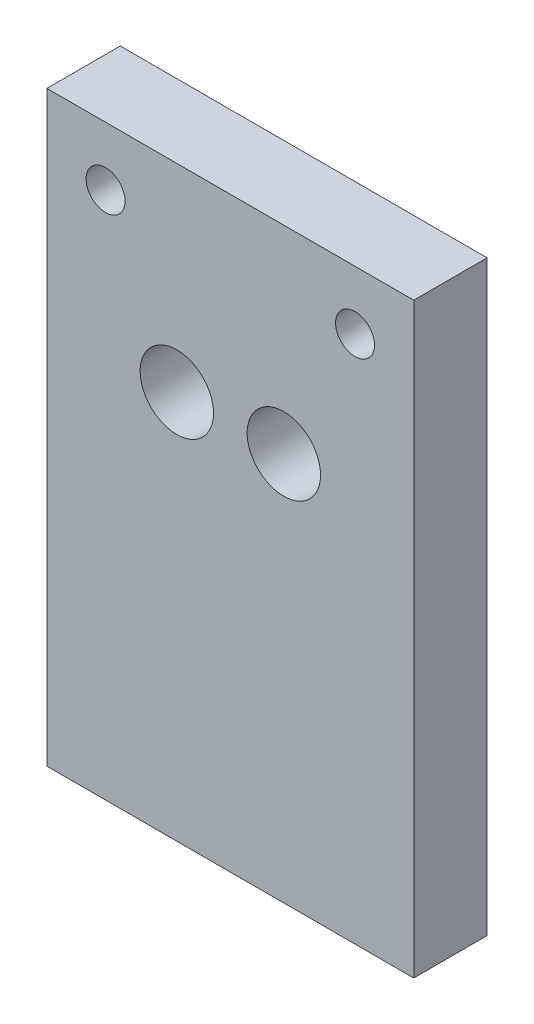
SolidWorks part; units mm, degrees
material "Acrylic (Medium-high impact)"
ref_plane "Front Plane" through (0, 0, 0) normal (0, 0, 1) x (1, 0, 0)
ref_plane "Top Plane" through (0, 0, 0) normal (0, 1, 0) x (1, 0, 0)
ref_plane "Right Plane" through (0, 0, 0) normal (1, 0, 0) x (0, 0, -1)
sketch "Sketch1" plane through (0, 0, 0) normal (0, 0, 1) x (1, 0, 0)
  line L1 (-31.75, 67.31) -> (31.75, 67.31)
  line L2 (-31.75, 67.31) -> (-31.75, -67.31)
  line L3 (-31.75, -67.31) -> (31.75, -67.31)
  line L4 (31.75, 67.31) -> (31.75, -67.31)
  line L5 (-31.75, 67.31) -> (31.75, -67.31) construction
  line L6 (-31.75, -67.31) -> (31.75, 67.31) construction
  circle A0 centre (-9.2608, 0) radius 6.35
  circle A1 centre (9.2608, 0) radius 6.35
  point P0 (0, 0)
  dimension "D3" = 12.7
  dimension "D4" = 12.7
  dimension "D1" = 63.5
  dimension "D2" = 134.62
  dimension "D5" = 9.2608
  dimension "D6" = 9.2608
extrude "Boss-Extrude1" add sketch "Sketch1" along normal blind 12.7
sketch "Sketch2" plane through (0, 0, 12.7) normal (0, 0, 1) x (1, 0, 0)
  line L0 (31.75, -67.31) -> (31.75, 67.31) construction
  line L1 (-31.75, 67.31) -> (31.75, 67.31)
  line L2 (-31.75, 67.31) -> (-31.75, 34.29)
  line L3 (-31.75, 34.29) -> (31.75, 34.29)
  line L4 (31.75, 67.31) -> (31.75, 34.29)
  dimension "D1" = 33.02
extrude "Cut-Extrude1" cut sketch "Sketch2" against normal through all
sketch "Sketch3" plane through (0, 0, 12.7) normal (0, 0, 1) x (1, 0, 0)
  line L0 (-9.2608, 0) -> (-9.2608, -83.7414) construction
hole_wizard "1/4 Clearance Hole1" positions "Sketch6" profile "Sketch5" hole size "1/4" standard "ANSI Inch" end condition through all
sketch "Sketch6" plane through (0, 0, 12.7) normal (0, 0, 1) x (1, 0, 0)
  line L0 (-31.75, 34.29) -> (31.75, 34.29) construction
  line L1 (-31.75, 34.29) -> (-31.75, -67.31) construction
  point P0 (-21.59, 24.13)
  dimension "D1" = 10.16
  dimension "D2" = 10.16
sketch "Sketch5" plane through (-21.59, 24.13, 12.7) normal (1, 0, 0) x (0, -1, 0)
  line L0 (0, 0) -> (0, 12.7)
  line L1 (0, 12.7) -> (3.3782, 12.7)
  line L2 (3.3782, 12.7) -> (3.3782, 0)
  line L5 (3.3782, 0) -> (0, 0)
  line L11 (0, -6.35) -> (0, 107.95) construction
  dimension "Thru Hole Dia." = 6.7564
  dimension "Thru Hole Depth" = 12.7
mirror "Mirror1" about plane through (0, 0, 0) normal (1, 0, 0) of "1/4 Clearance Hole1"
hole_wizard "#10-32 Tapped Hole1" positions "Sketch7" profile "Sketch8" tap size "#10-32" standard "ANSI Inch"
sketch "Sketch7" plane through (0, -67.31, 0) normal (0, -1, 0) x (-1, 0, 0)
  line L0 (31.75, -12.7) -> (-31.75, -12.7) construction
  line L1 (31.75, -12.7) -> (31.75, 0) construction
  point P0 (21.59, -6.35)
  dimension "D1" = 6.35
  dimension "D2" = 10.16
sketch "Sketch8" plane through (-21.59, -67.31, 6.35) normal (1, 0, 0) x (0, 0, -1)
  line L0 (0, 0) -> (0, 13.9133)
  line L1 (0, 13.9133) -> (2.0193, 12.7)
  line L2 (2.0193, 12.7) -> (2.0193, 0)
  line L5 (2.0193, 0) -> (0, 0)
  line L10 (0, 13.9133) -> (-2.0193, 12.7) construction
  line L11 (0, -6.35) -> (0, 107.95) construction
  dimension "Tap Drill Dia." = 4.0386
  dimension "Tap Drill Depth" = 12.7
  dimension "Drill Angle" = 118
cosmetic thread "Hole Thread1" parameters "D1"=9.652, "D2"=4.826
mirror "Mirror2" about plane through (0, 0, 0) normal (1, 0, 0) of "#10-32 Tapped Hole1"
